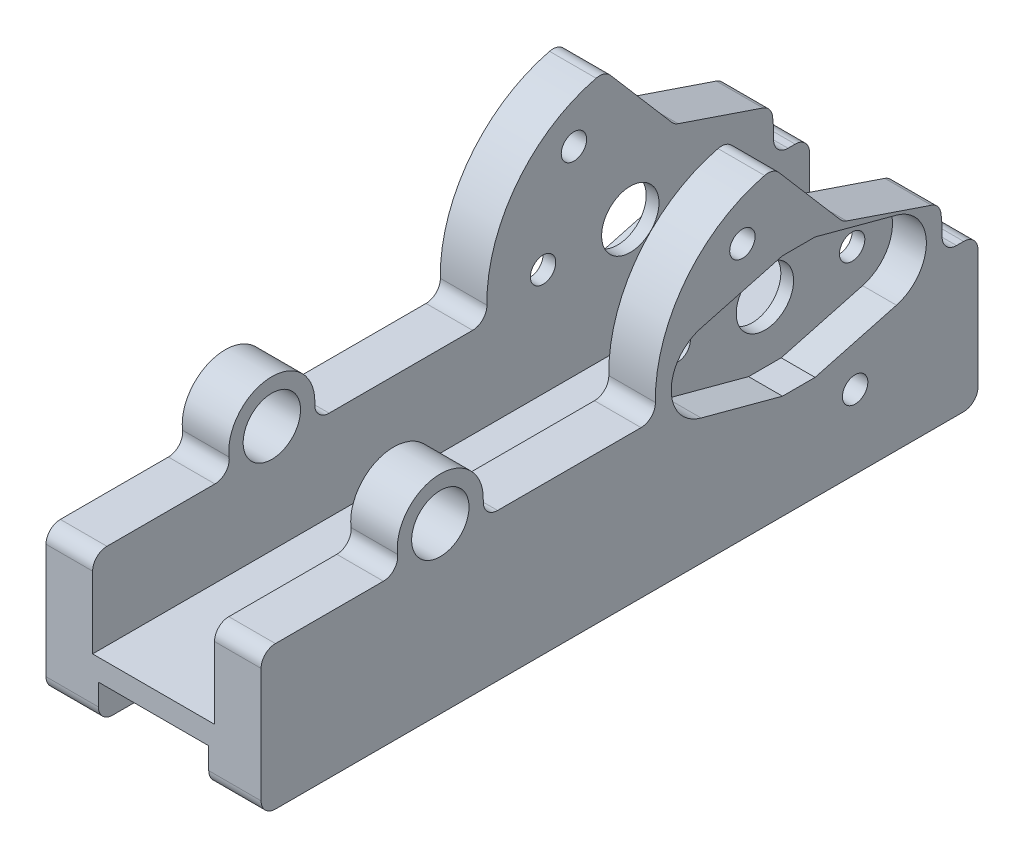
SolidWorks part; units mm, degrees
ref_plane "Front Plane" through (0, 0, 0) normal (0, 0, 1) x (1, 0, 0)
ref_plane "Top Plane" through (0, 0, 0) normal (0, 1, 0) x (1, 0, 0)
ref_plane "Right Plane" through (0, 0, 0) normal (1, 0, 0) x (0, 0, -1)
sketch "Sketch1" plane through (0, 0, 0) normal (0, 1, 0) x (1, 0, 0)
  line L1 (-19.05, -63.5) -> (19.05, -63.5)
  line L2 (-19.05, -63.5) -> (-19.05, 63.5)
  line L3 (-19.05, 63.5) -> (19.05, 63.5)
  line L4 (19.05, -63.5) -> (19.05, 63.5)
  line L5 (-19.05, -63.5) -> (19.05, 63.5) construction
  line L6 (-19.05, 63.5) -> (19.05, -63.5) construction
  point P0 (0, 0)
  dimension "D1" = 38.1
  dimension "D2" = 127
extrude "Boss-Extrude1" add sketch "Sketch1" along normal blind 57.15
sketch "Sketch2" plane through (0, 57.15, 0) normal (0, 1, 0) x (1, 0, 0)
  line L1 (-10.795, -158.75) -> (10.795, -158.75)
  line L2 (-10.795, -158.75) -> (-10.795, 95.25)
  line L3 (-10.795, 95.25) -> (10.795, 95.25)
  line L4 (10.795, -158.75) -> (10.795, 95.25)
  line L5 (-10.795, -158.75) -> (10.795, 95.25) construction
  line L6 (-10.795, 95.25) -> (10.795, -158.75) construction
  point P0 (0, -31.75)
  dimension "D1" = 254
  dimension "D2" = 21.59
  dimension "D3" = 31.75
extrude "Cut-Extrude1" cut sketch "Sketch2" against normal blind 46.99
sketch "Sketch3" plane through (19.05, 0, 0) normal (1, 0, 0) x (0, 0, -1)
  line L0 (-63.5, 57.15) -> (-63.5, 0) construction
  line L1 (-63.5, 0) -> (63.5, 0) construction
  circle A0 centre (-31.75, 29.21) radius 5.08
  circle A1 centre (31.75, 29.21) radius 5.08
  dimension "D1" = 10.16
  dimension "D2" = 31.75
  dimension "D3" = 29.21
  dimension "D4" = 63.5
extrude "Cut-Extrude2" cut sketch "Sketch3" against normal through all both and the other way through all
sketch "Sketch11" plane through (-19.05, 0, 0) normal (-1, 0, 0) x (0, 0, 1)
  line L0 (63.5, 25.4) -> (38.3491, 25.4)
  line L1 (63.5, 57.15) -> (63.5, 0) construction
  line L2 (-63.5, 57.15) -> (-63.5, 0) construction
  line L3 (-63.5, 0) -> (63.5, 0) construction
  line L9 (-63.5, 26.142) -> (-63.5, 57.15)
  line L11 (63.5, 57.15) -> (63.5, 25.4)
  line L12 (24.7749, 26.142) -> (-6.536, 26.142)
  line L14 (-63.5, 26.142) -> (-63.5, 67.5531)
  line L15 (-63.5, 67.5531) -> (63.5, 67.5531)
  line L16 (63.5, 67.5531) -> (63.5, 57.15)
  line L17 (-56.964, 26.142) -> (-63.5, 26.142)
  arc A0 (38.3491, 25.4) -> (24.7749, 26.142) centre (31.75, 29.21) ccw
  circle A2 centre (31.75, 29.21) radius 5.08 construction
  arc A3 (-6.536, 26.142) -> (-56.964, 26.142) centre (-31.75, 29.21) ccw
  point P2 (-54.9137, 18.7887)
  line M4 (63.5, 0) -> (63.5, 57.15)
  line M5 (63.5, 57.15) -> (-63.5, 57.15)
  line M6 (-63.5, 57.15) -> (-63.5, 0)
  dimension "D1" = 2.54
  dimension "D3" = 25.4
  dimension "D2" = 25.4
extrude "Cut-Extrude8" cut sketch "Sketch11" against normal through all contours A3 L12 A0 L0 M4 M5 M6 region at (-19.05, 43.5431, 12.719)
sketch "Sketch12" plane through (0, 0, 63.5) normal (0, 0, 1) x (1, 0, 0)
  line L1 (-9.779, -6.35) -> (9.779, -6.35)
  line L2 (-9.779, -6.35) -> (-9.779, 6.35)
  line L3 (-9.779, 6.35) -> (9.779, 6.35)
  line L4 (9.779, -6.35) -> (9.779, 6.35)
  line L5 (-9.779, -6.35) -> (9.779, 6.35) construction
  line L6 (-9.779, 6.35) -> (9.779, -6.35) construction
  point P0 (0, 0)
  dimension "D1" = 19.558
  dimension "D2" = 12.7
extrude "Cut-Extrude9" cut sketch "Sketch12" against normal through all
sketch "Sketch13" plane through (0, 10.16, 0) normal (0, 1, 0) x (1, 0, 0)
  line L0 (10.795, -63.5) -> (-10.795, -63.5) construction
  circle A0 centre (0, -44.45) radius 2.413
  circle A1 centre (0, 57.15) radius 2.413
  circle A2 centre (0, 6.35) radius 2.413
  dimension "D1" = 4.826
  dimension "D2" = 19.05
  dimension "D3" = 101.6
  dimension "2" = 50.8
extrude "Cut-Extrude10" cut sketch "Sketch13" against normal through all
sketch "Sketch14" plane through (-19.05, 0, 0) normal (-1, 0, 0) x (0, 0, 1)
  line L0 (-27.5129, 47.8677) -> (-16.9651, 41.3536) construction
  line L2 (-22.239, 44.6107) -> (-21.7665, 45.3757) construction
  line L3 (-22.0027, 44.9932) -> (-41.7335, 13.0443) construction
  circle A0 centre (-31.75, 29.21) radius 19 construction
  arc A1 (-24.6397, 49.2351) -> (-26.1454, 44.9945) centre (-25.3925, 47.1148) ccw construction
  arc A2 (-20.1464, 41.2897) -> (-17.029, 44.535) centre (-18.5877, 42.9123) ccw construction
  point P17 (-21.7665, 45.3757)
  point P25 (-41.7335, 13.0443)
  point P31 (-41.7335, 13.0443)
  point P33 (-21.7665, 45.3757)
  dimension "D1" = 38
hole_wizard "#3 Clearance Hole1" positions "Sketch14" profile "Sketch15" hole size "Ø4.0" standard "ANSI Metric" end condition through all
sketch "Sketch15" plane through (-19.05, 45.3757, -21.7665) normal (0, 1, 0) x (0, 0, 1)
  line L0 (0, 0) -> (0, 38.1)
  line L1 (0, 38.1) -> (2.25, 38.1)
  line L2 (2.25, 38.1) -> (2.25, 0)
  line L5 (2.25, 0) -> (0, 0)
  line L11 (0, -6.35) -> (0, 107.95) construction
  dimension "Thru Hole Dia." = 4.5
  dimension "Thru Hole Depth" = 38.1
fillet "Fillet2" [suppressed] radius 6.35
sketch "Sketch16" plane through (-19.05, 0, 0) normal (-1, 0, 0) x (0, 0, 1)
  line L0 (-47.2, 29.21) -> (-16.3, 29.21) construction
  circle A0 centre (-47.2, 29.21) radius 2.2479
  circle A1 centre (-16.3, 29.21) radius 2.2479
  arc A2 (-31.3559, 29.8481) -> (-32.1441, 28.5719) centre (-31.75, 29.21) ccw construction
  point P0 (-47.2, 29.21)
  point P5 (-31.75, 29.21)
  dimension "D2" = 4.4958
  dimension "D3" = 4.4958
  dimension "D1" = 30.9
extrude "Cut-Extrude11" cut sketch "Sketch16" against normal through all
sketch "Sketch17" plane through (-19.05, 0, 0) normal (-1, 0, 0) x (0, 0, 1)
  line L12 (-56.964, 26.142) -> (-63.5, 26.142)
  line L13 (-63.5, 26.142) -> (-63.5, 0)
  line L14 (-63.5, 0) -> (63.5, 0)
  line L15 (63.5, 0) -> (63.5, 25.4)
  line L16 (63.5, 25.4) -> (38.3491, 25.4)
  line L17 (24.7749, 26.142) -> (-6.536, 26.142)
  line L18 (-56.964, 26.142) -> (-63.5, 26.142)
  line L19 (-63.5, 26.142) -> (-63.5, 0)
  line L20 (-63.5, 0) -> (63.5, 0)
  line L21 (63.5, 0) -> (63.5, 25.4)
  line L23 (24.7749, 26.142) -> (-6.536, 26.142)
  line L26 (63.5, 25.4) -> (38.3491, 25.4)
  arc A4 (38.3491, 25.4) -> (24.7749, 26.142) centre (31.75, 29.21) ccw
  arc A5 (-6.536, 26.142) -> (-56.964, 26.142) centre (-31.75, 29.21) ccw
  arc A7 (-6.536, 26.142) -> (-56.964, 26.142) centre (-31.75, 29.21) ccw
  arc A10 (38.3491, 25.4) -> (24.7749, 26.142) centre (31.75, 29.21) ccw
  dimension "D1" = 0
sketch "Sketch21" plane through (-19.05, 0, 0) normal (-1, 0, 0) x (0, 0, 1)
  line L0 (-49.0511, 36.1162) -> (-34.6367, 39.9798)
  line L1 (-34.6367, 39.9798) -> (-28.8633, 39.9798)
  line L2 (-28.8633, 39.9798) -> (-14.4489, 36.1162)
  line L4 (-14.4489, 22.3038) -> (-28.8633, 18.4402)
  line L5 (-28.8633, 18.4402) -> (-34.6367, 18.4402)
  line L6 (-34.6367, 18.4402) -> (-49.0511, 22.3038)
  arc A0 (-49.0511, 36.1162) -> (-49.0511, 22.3038) centre (-47.2, 29.21) ccw
  arc A1 (-14.4489, 36.1162) -> (-14.4489, 22.3038) centre (-16.3, 29.21) cw
extrude "Cut-Extrude13" cut sketch "Sketch21" against normal blind 6
sketch "Sketch22" plane through (-19.05, 0, 0) normal (-1, 0, 0) x (0, 0, 1)
  line L0 (-56.6832, 34.057) -> (-39.5707, 39.8622)
  line L1 (-39.5707, 39.8622) -> (-27.2512, 54.2084)
  line L2 (-27.2512, 54.2084) -> (-28.6882, 55.7976)
  line L3 (-28.6882, 55.7976) -> (-55.153, 53.2432)
  line L4 (-55.153, 53.2432) -> (-63.3902, 32.0211)
  line L5 (-63.3902, 32.0211) -> (-56.6832, 34.057)
  arc A0 (-6.536, 26.142) -> (-56.964, 26.142) centre (-31.75, 29.21) ccw construction
extrude "Cut-Extrude14" cut sketch "Sketch22" against normal through all
fillet "Fillet3" radius 2.54 22 edges at (-14.9225, 25.4, 63.5) (14.9225, 25.4, 63.5) (-14.4145, 0, 63.5) (14.4145, 0, 63.5) (14.4145, 0, -63.5) (-14.4145, 0, -63.5) (-14.9225, 26.142, -63.5) (14.9225, 26.142, -63.5) (-14.9225, 26.142, -6.536) (14.9225, 26.142, -6.536) (14.9225, 54.2084, -27.2512) (-14.9225, 54.2084, -27.2512) (-14.9225, 39.8622, -39.5707) (14.9225, 39.8622, -39.5707) (14.9225, 34.057, -56.6832) (-14.9225, 34.057, -56.6832) (-14.9225, 26.142, -56.964) (14.9225, 26.142, -56.964) (14.9225, 26.142, 24.7749) (14.9225, 25.4, 38.3491) (-14.9225, 25.4, 38.3491) (-14.9225, 26.142, 24.7749)
ref_plane "Plane1" through (0, 0, 0) normal (1, 0, 0) x (0, 0, -1)
mirror "Mirror1" about plane through (0, 0, 0) normal (1, 0, 0) of "Cut-Extrude13"
